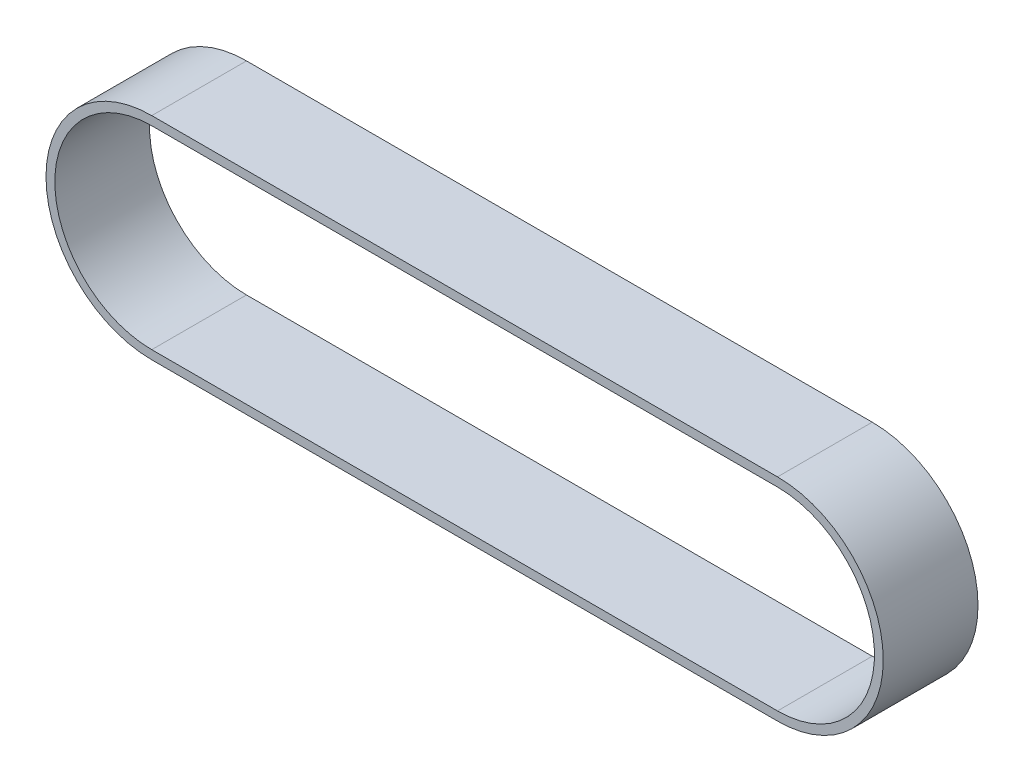
SolidWorks part; units mm, degrees
ref_plane "Front Plane" through (0, 0, 0) normal (0, 0, 1) x (1, 0, 0)
ref_plane "Top Plane" through (0, 0, 0) normal (0, 1, 0) x (1, 0, 0)
ref_plane "Right Plane" through (0, 0, 0) normal (1, 0, 0) x (0, 0, -1)
sketch "Sketch1" plane through (0, 0, 0) normal (0, 0, 1) x (1, 0, 0)
  line L0 (-50.4004, 0) -> (69.3544, 0) construction
  line L1 (0, 85.0776) -> (0, -72.5852) construction
  line L2 (-71, 0) -> (71, 0) construction
  line L3 (-71, 22) -> (71, 22)
  line L4 (-71, -22) -> (71, -22)
  line L5 (-71, 24) -> (71, 24)
  line L6 (-71, -24) -> (71, -24)
  arc A0 (71, -24) -> (71, 24) centre (71, 0) ccw
  arc A1 (-71, 24) -> (-71, -24) centre (-71, 0) ccw
  arc A2 (-71, 22) -> (-71, -22) centre (-71, 0) ccw
  arc A3 (71, -22) -> (71, 22) centre (71, 0) ccw
  point P11 (0, 0)
  dimension "D1" = 22
  dimension "D2" = 2
  dimension "D3" = 142
extrude "Boss-Extrude1" add sketch "Sketch1" along normal blind 21.5
